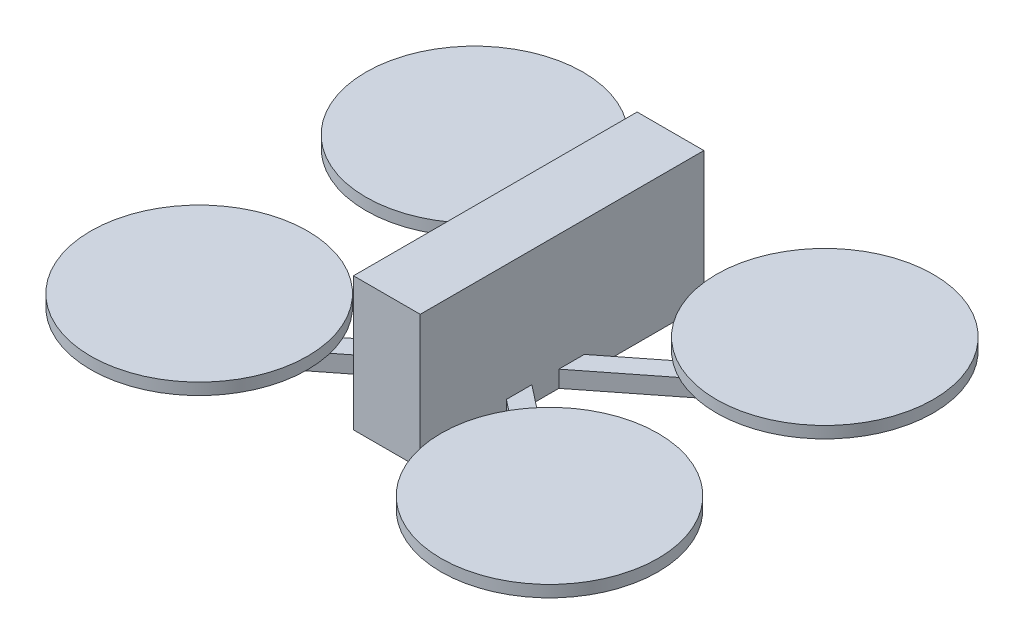
SolidWorks part; units mm, degrees
ref_plane "前视基准面" through (0, 0, 0) normal (0, 0, 1) x (1, 0, 0)
ref_plane "上视基准面" through (0, 0, 0) normal (0, 1, 0) x (1, 0, 0)
ref_plane "右视基准面" through (0, 0, 0) normal (1, 0, 0) x (0, 0, -1)
other "Configuration Table"
sketch "Sketch2" plane through (0, 0, 0) normal (0, 1, 0) x (1, 0, 0)
  line L0 (-105, 82.5) -> (105, -82.5)
  line L1 (-20, 95) -> (20, 95)
  line L2 (-20, 95) -> (-20, -75)
  line L3 (-20, -75) -> (20, -75)
  line L4 (20, 95) -> (20, -75)
  line L5 (-105, 82.5) -> (105, 82.5)
  line L6 (-105, 82.5) -> (-105, -82.5)
  line L7 (-105, -82.5) -> (105, -82.5)
  line L8 (105, 82.5) -> (105, -82.5)
  line L9 (105, 82.5) -> (-105, -82.5)
  line L10 (-108.7069, 77.7821) -> (101.2931, -87.2179)
  line L11 (101.2931, 87.2179) -> (-108.7069, -77.7821)
  line L12 (-101.2931, 87.2179) -> (108.7069, -77.7821)
  line L13 (108.7069, 77.7821) -> (-101.2931, -87.2179)
  circle A0 centre (-105, 82.5) radius 15
  circle A1 centre (105, 82.5) radius 15
  circle A2 centre (105, -82.5) radius 15
  circle A3 centre (-105, -82.5) radius 15
  point P0 (0, 0)
  dimension "D1" = 170
  dimension "D2" = 40
  dimension "D3" = 95
  dimension "D4" = 20
  dimension "D5" = 165
  dimension "D6" = 210
  dimension "D7" = 105
  dimension "D8" = 82.5
  dimension "D9" = 6
  dimension "D10" = 6
extrude "Boss-Extrude2" add sketch "Sketch2" along normal blind 80 contours L2 L3 L4 L1
extrude "Boss-Extrude3" add sketch "Sketch2<3>" along normal blind 10 contours A3 L9 L2 L11 | A3 L13 L2 L9 | A2 L12 L4 L0 | A2 L0 L4 L10 | A1 L11 L4 L9 | A1 L9 L4 L13 | A0 L10 L2 L0 | A0 L0 L2 L12 region at (-55.8415, 0, -47.6665) region at (-57.7028, 0, -41.4831) region at (-57.7028, 0, 41.4831) region at (55.8415, 0, -47.6665) region at (-55.8415, 0, 47.6665) region at (57.7028, 0, 41.4831) region at (55.8415, 0, 47.6665) region at (57.7028, 0, -41.4831)
sketch "Sketch2<3>" plane through (0, 0, 0) normal (0, 1, 0) x (1, 0, 0) same geometry as "Sketch2"
extrude "Boss-Extrude4" add sketch "Sketch2<4>" along normal blind 25 contours A0 | A1 | A2 | A3
sketch "Sketch2<4>" plane through (0, 0, 0) normal (0, 1, 0) x (1, 0, 0) same geometry as "Sketch2"
sketch "Sketch3" plane through (0, 25, 0) normal (0, 1, 0) x (1, 0, 0)
  circle A0 centre (-105, -82.5) radius 65
  circle A1 centre (105, -82.5) radius 65
  circle A2 centre (105, 82.5) radius 65
  circle A3 centre (-105, 82.5) radius 65
extrude "Boss-Extrude5" add sketch "Sketch3" along normal blind 7
